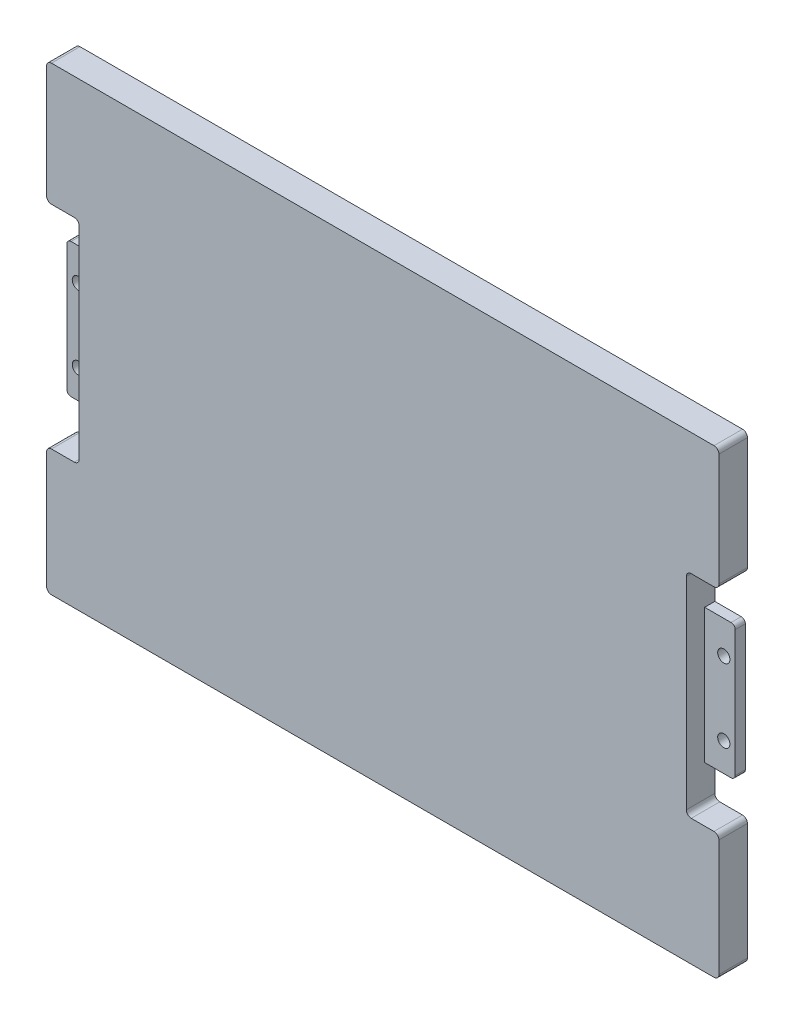
SolidWorks part; units mm, degrees
material "PBTP"
ref_plane "Front" through (0, 0, 0) normal (0, 0, 1) x (1, 0, 0)
ref_plane "Top" through (0, 0, 0) normal (0, 1, 0) x (1, 0, 0)
ref_plane "Right" through (0, 0, 0) normal (1, 0, 0) x (0, 0, -1)
sketch "Эскиз1" plane through (0, 0, 0) normal (0, 0, 1) x (1, 0, 0)
  line L0 (1.2018, 83) -> (6.7982, 83)
  line L1 (1.2018, 0) -> (163.7982, 0)
  line L2 (0, 1.2018) -> (0, 29.7982)
  line L3 (1.2018, 113) -> (163.7982, 113)
  line L4 (165, 1.2018) -> (165, 29.7982)
  line L5 (8, 81.7982) -> (8, 32.2018)
  line L6 (6.7982, 31) -> (1.2018, 31)
  line L7 (0, 84.2018) -> (0, 111.7982)
  line L8 (158.2018, 83) -> (163.7982, 83)
  line L9 (158.2018, 31) -> (163.7982, 31)
  line L10 (157, 81.7982) -> (157, 32.2018)
  line L11 (165, 84.2018) -> (165, 111.7982)
  arc A0 (0, 111.7982) -> (1.2018, 113) centre (1.2018, 111.7982) cw
  arc A1 (6.7982, 83) -> (8, 81.7982) centre (6.7982, 81.7982) cw
  arc A2 (1.2018, 83) -> (0, 84.2018) centre (1.2018, 84.2018) cw
  arc A3 (8, 32.2018) -> (6.7982, 31) centre (6.7982, 32.2018) cw
  arc A4 (1.2018, 31) -> (0, 29.7982) centre (1.2018, 29.7982) ccw
  arc A5 (1.2018, 0) -> (0, 1.2018) centre (1.2018, 1.2018) cw
  arc A6 (163.7982, 0) -> (165, 1.2018) centre (163.7982, 1.2018) ccw
  arc A7 (157, 32.2018) -> (158.2018, 31) centre (158.2018, 32.2018) ccw
  arc A8 (163.7982, 31) -> (165, 29.7982) centre (163.7982, 29.7982) cw
  arc A9 (158.2018, 83) -> (157, 81.7982) centre (158.2018, 81.7982) ccw
  arc A10 (163.7982, 83) -> (165, 84.2018) centre (163.7982, 84.2018) ccw
  arc A11 (163.7982, 113) -> (165, 111.7982) centre (163.7982, 111.7982) cw
  point P15 (0, 113)
  point P18 (8, 83)
  point P21 (0, 83)
  point P24 (8, 31)
  point P29 (0, 0)
  point P32 (165, 0)
  point P41 (165, 83)
  dimension "D9" = 1.2018
  dimension "D1" = 113
  dimension "D2" = 165
  dimension "D3" = 30
  dimension "D4" = 31
  dimension "D5" = 8
  dimension "D6" = 8
  dimension "D7" = 30
  dimension "D8" = 31
extrude "Бобышка-Вытянуть1" add sketch "Эскиз1" along normal blind 7
sketch "Эскиз2" plane through (0, 0, 0) normal (0, 0, -1) x (-1, 0, 0)
  line L0 (-163.7982, 113) -> (-1.2018, 113) construction
  line L1 (-161.7982, 111) -> (-3.2018, 111)
  line L2 (-163, 109.7982) -> (-163, 86.2018)
  line L3 (-161.7982, 2) -> (-3.2018, 2)
  line L4 (-2, 109.7982) -> (-2, 86.2018)
  line L5 (-1.2018, 0) -> (-163.7982, 0) construction
  line L6 (-165, 1.2018) -> (-165, 29.7982) construction
  line L7 (0, 111.7982) -> (0, 84.2018) construction
  line L8 (-161.7982, 85) -> (-156.2018, 85)
  line L9 (-155, 83.7982) -> (-155, 74.8)
  line L10 (-156.2018, 29) -> (-161.7982, 29)
  line L11 (-163, 27.7982) -> (-163, 3.2018)
  line L12 (-158.2018, 83) -> (-163.7982, 83) construction
  line L13 (-157, 32.2018) -> (-157, 81.7982) construction
  line L14 (-163.7982, 31) -> (-158.2018, 31) construction
  line L15 (-3.2018, 85) -> (-8.7982, 85)
  line L16 (-10, 83.7982) -> (-10, 30.2018)
  line L17 (-8.7982, 29) -> (-3.2018, 29)
  line L18 (-8, 81.7982) -> (-8, 32.2018) construction
  line L19 (-6.7982, 31) -> (-1.2018, 31) construction
  line L20 (-2, 27.7982) -> (-2, 3.2018)
  line L21 (-155, 74.8) -> (-155, 70.5)
  line L25 (-155, 70.5) -> (-155, 30.2018)
  circle A0 centre (-82.5, 57) radius 6
  arc A1 (-161.7982, 85) -> (-163, 86.2018) centre (-161.7982, 86.2018) cw
  arc A2 (-156.2018, 85) -> (-155, 83.7982) centre (-156.2018, 83.7982) cw
  arc A3 (-155, 30.2018) -> (-156.2018, 29) centre (-156.2018, 30.2018) cw
  arc A4 (-161.7982, 29) -> (-163, 27.7982) centre (-161.7982, 27.7982) ccw
  arc A5 (-163, 3.2018) -> (-161.7982, 2) centre (-161.7982, 3.2018) ccw
  arc A6 (-3.2018, 2) -> (-2, 3.2018) centre (-3.2018, 3.2018) ccw
  arc A7 (-3.2018, 29) -> (-2, 27.7982) centre (-3.2018, 27.7982) cw
  arc A8 (-10, 30.2018) -> (-8.7982, 29) centre (-8.7982, 30.2018) ccw
  arc A9 (-8.7982, 85) -> (-10, 83.7982) centre (-8.7982, 83.7982) ccw
  arc A10 (-3.2018, 85) -> (-2, 86.2018) centre (-3.2018, 86.2018) ccw
  arc A11 (-3.2018, 111) -> (-2, 109.7982) centre (-3.2018, 109.7982) cw
  arc A12 (-161.7982, 111) -> (-163, 109.7982) centre (-161.7982, 109.7982) ccw
  point P18 (-161, 83)
  point P31 (-4, 31)
  point P32 (-6, 29)
  point P45 (-155, 85)
  point P50 (-163, 29)
  point P57 (-2, 29)
  dimension "D12" = 12
  dimension "D17" = 1.2018
  dimension "D1" = 2
  dimension "D2" = 2
  dimension "D3" = 2
  dimension "D4" = 2
  dimension "D5" = 2
  dimension "D6" = 2
  dimension "D7" = 2
  dimension "D8" = 2
  dimension "D9" = 2
  dimension "D10" = 2
  dimension "D11" = 56
  dimension "D13" = 82.5
extrude "Вырез-Вытянуть1" cut sketch "Эскиз2" against normal blind 5.8
sketch "Эскиз3" plane through (0, 0, 5.8) normal (0, 0, -1) x (-1, 0, 0)
  line L0 (-1.2018, 0) -> (-163.7982, 0) construction
  line L1 (-120, 31) -> (-103, 31)
  line L2 (-121, 30) -> (-121, 19)
  line L3 (-120, 18) -> (-103, 18)
  line L4 (-102, 30) -> (-102, 19)
  line L5 (-165, 1.2018) -> (-165, 29.7982) construction
  line L6 (-41.4032, 94.6438) -> (-44.49, 94.6438)
  line L7 (-52.1501, 97.2393) -> (-39.1501, 97.2393)
  line L8 (-53.1501, 96.2393) -> (-53.1501, 83.2393)
  line L9 (-52.1501, 82.2393) -> (-39.1501, 82.2393)
  line L10 (-38.1501, 96.2393) -> (-38.1501, 83.2393)
  line L11 (-44.49, 94.6438) -> (-48.7847, 93.6372)
  line L12 (-48.7847, 93.6372) -> (-48.7847, 92.6306)
  line L13 (-48.7847, 92.6306) -> (-44.49, 93.6372)
  line L14 (-44.49, 93.6372) -> (-41.4032, 93.6372)
  line L15 (-41.4032, 93.6372) -> (-41.4032, 94.6438)
  line L16 (-48.7847, 91.7748) -> (-44.49, 92.6306)
  line L17 (-44.49, 92.6306) -> (-44.49, 91.7748)
  line L18 (-44.49, 91.7748) -> (-48.7847, 90.919)
  line L19 (-48.7847, 90.919) -> (-48.7847, 91.7748)
  line L20 (-48.7847, 90.0551) -> (-44.49, 90.9109)
  line L21 (-44.49, 90.9109) -> (-44.49, 90.0551)
  line L22 (-44.49, 90.0551) -> (-48.7847, 89.0679)
  line L23 (-48.7847, 90.0551) -> (-48.7847, 89.0679)
  line L24 (-48.7847, 88.2165) -> (-44.49, 89.0679)
  line L25 (-44.49, 89.0679) -> (-41.4032, 89.0679)
  line L26 (-41.4032, 89.0679) -> (-41.4032, 88.3169)
  line L27 (-41.4032, 88.3169) -> (-44.3412, 88.3169)
  line L28 (-44.3412, 88.3169) -> (-48.7847, 87.436)
  line L29 (-48.7847, 87.436) -> (-48.7847, 88.2165)
  line L30 (-48.6096, 93.8881) -> (-44.8588, 94.806)
  line L31 (-44.8588, 94.806) -> (-44.8588, 95.9138)
  line L32 (-44.8588, 95.9138) -> (-46.7342, 95.17)
  line L33 (-46.7342, 95.17) -> (-48.6096, 95.7398)
  line L34 (-48.6096, 95.7398) -> (-48.6096, 93.8881)
  line L35 (-48.6096, 87.0068) -> (-44.8588, 87.7157)
  line L36 (-44.8588, 87.7157) -> (-44.8588, 86.3281)
  line L37 (-44.8588, 86.3281) -> (-46.7342, 86.675)
  line L38 (-46.7342, 86.675) -> (-48.6096, 85.77)
  line L39 (-48.6096, 85.77) -> (-48.6096, 87.0068)
  arc A0 (-103, 18) -> (-102, 19) centre (-103, 19) ccw
  arc A1 (-121, 19) -> (-120, 18) centre (-120, 19) ccw
  arc A2 (-103, 31) -> (-102, 30) centre (-103, 30) cw
  arc A3 (-120, 31) -> (-121, 30) centre (-120, 30) ccw
  arc A4 (-39.1501, 97.2393) -> (-38.1501, 96.2393) centre (-39.1501, 96.2393) cw
  arc A5 (-39.1501, 82.2393) -> (-38.1501, 83.2393) centre (-39.1501, 83.2393) ccw
  arc A6 (-53.1501, 83.2393) -> (-52.1501, 82.2393) centre (-52.1501, 83.2393) ccw
  arc A7 (-52.1501, 97.2393) -> (-53.1501, 96.2393) centre (-52.1501, 96.2393) ccw
  point P10 (-102, 18)
  point P13 (-121, 18)
  point P16 (-102, 31)
  point P25 (-38.1501, 97.2393)
  point P30 (-53.1501, 82.2393)
  point P33 (-53.1501, 97.2393)
  dimension "D7" = 1
  dimension "D10" = 1
  dimension "D1" = 13
  dimension "D2" = 19
  dimension "D3" = 18
  dimension "D4" = 31
  dimension "D5" = 44
  dimension "D6" = 63
  dimension "D8" = 15
  dimension "D9" = 15
extrude "Вырез-Вытянуть2" cut sketch "Эскиз3" against normal blind 0.2
sketch "Эскиз4" plane through (0, 0, 0) normal (0, 0, -1) x (-1, 0, 0)
  line L0 (-163.5, 73) -> (-157, 73)
  line L1 (-157, 32.2018) -> (-157, 81.7982) construction
  line L2 (-164.5, 72) -> (-164.5, 41)
  line L3 (-163.5, 40) -> (-157, 40)
  line L4 (-163.7982, 113) -> (-1.2018, 113) construction
  line L5 (-1.2018, 0) -> (-163.7982, 0) construction
  line L6 (-8, 73) -> (-1.5, 73)
  line L7 (-8, 81.7982) -> (-8, 32.2018) construction
  line L8 (-0.5, 72) -> (-0.5, 41)
  line L9 (-1.5, 40) -> (-8, 40)
  line L10 (-8, 73) -> (-8, 40)
  line L18 (0, 1.2018) -> (0, 29.7982)
  line L19 (-1.2018, 31) -> (-6.7982, 31)
  line L20 (-8, 32.2018) -> (-8, 81.7982)
  line L21 (-6.7982, 83) -> (-1.2018, 83)
  line L22 (0, 84.2018) -> (0, 111.7982)
  line L23 (-1.2018, 113) -> (-163.7982, 113)
  line L24 (-165, 111.7982) -> (-165, 84.2018)
  line L25 (-163.7982, 83) -> (-158.2018, 83)
  line L26 (-157, 81.7982) -> (-157, 32.2018)
  line L27 (-158.2018, 31) -> (-163.7982, 31)
  line L28 (-165, 29.7982) -> (-165, 1.2018)
  line L29 (-163.7982, 0) -> (-1.2018, 0)
  line L38 (-157, 73) -> (-157, 40)
  circle A0 centre (-161.7, 65) radius 1.5
  circle A1 centre (-161.7, 47) radius 1.5
  circle A2 centre (-3.3, 65) radius 1.5
  circle A3 centre (-3.3, 47) radius 1.5
  arc A4 (-0.5, 41) -> (-1.5, 40) centre (-1.5, 41) cw
  arc A5 (-164.5, 41) -> (-163.5, 40) centre (-163.5, 41) ccw
  arc A6 (-163.5, 73) -> (-164.5, 72) centre (-163.5, 72) ccw
  arc A7 (-1.5, 73) -> (-0.5, 72) centre (-1.5, 72) cw
  arc A16 (0, 111.7982) -> (-1.2018, 113) centre (-1.2018, 111.7982) ccw
  arc A17 (0, 111.7982) -> (-1.2018, 113) centre (-1.2018, 111.7982) ccw
  arc A18 (-163.7982, 113) -> (-165, 111.7982) centre (-163.7982, 111.7982) ccw
  arc A19 (-163.7982, 113) -> (-165, 111.7982) centre (-163.7982, 111.7982) ccw
  arc A20 (-165, 84.2018) -> (-163.7982, 83) centre (-163.7982, 84.2018) ccw
  arc A21 (-165, 84.2018) -> (-163.7982, 83) centre (-163.7982, 84.2018) ccw
  arc A22 (-157, 81.7982) -> (-158.2018, 83) centre (-158.2018, 81.7982) ccw
  arc A23 (-157, 81.7982) -> (-158.2018, 83) centre (-158.2018, 81.7982) ccw
  arc A24 (-158.2018, 31) -> (-157, 32.2018) centre (-158.2018, 32.2018) ccw
  arc A25 (-158.2018, 31) -> (-157, 32.2018) centre (-158.2018, 32.2018) ccw
  arc A26 (-163.7982, 31) -> (-165, 29.7982) centre (-163.7982, 29.7982) ccw
  arc A27 (-163.7982, 31) -> (-165, 29.7982) centre (-163.7982, 29.7982) ccw
  arc A28 (-165, 1.2018) -> (-163.7982, 0) centre (-163.7982, 1.2018) ccw
  arc A29 (-165, 1.2018) -> (-163.7982, 0) centre (-163.7982, 1.2018) ccw
  arc A30 (-1.2018, 0) -> (0, 1.2018) centre (-1.2018, 1.2018) ccw
  arc A31 (-1.2018, 0) -> (0, 1.2018) centre (-1.2018, 1.2018) ccw
  arc A32 (0, 29.7982) -> (-1.2018, 31) centre (-1.2018, 29.7982) ccw
  arc A33 (0, 29.7982) -> (-1.2018, 31) centre (-1.2018, 29.7982) ccw
  arc A34 (-8, 32.2018) -> (-6.7982, 31) centre (-6.7982, 32.2018) ccw
  arc A35 (-8, 32.2018) -> (-6.7982, 31) centre (-6.7982, 32.2018) ccw
  arc A36 (-6.7982, 83) -> (-8, 81.7982) centre (-6.7982, 81.7982) ccw
  arc A37 (-6.7982, 83) -> (-8, 81.7982) centre (-6.7982, 81.7982) ccw
  arc A38 (-1.2018, 83) -> (0, 84.2018) centre (-1.2018, 84.2018) ccw
  arc A39 (-1.2018, 83) -> (0, 84.2018) centre (-1.2018, 84.2018) ccw
  dimension "D8" = 48
  dimension "D9" = 18
  dimension "D15" = 3
  dimension "D16" = 3
  dimension "D17" = 3
  dimension "D18" = 3
  dimension "D21" = 1
  dimension "D22" = 1
  dimension "D1" = 7.5
  dimension "D2" = 40
  dimension "D3" = 40
  dimension "D5" = 7.5
  dimension "D6" = 40
  dimension "D7" = 40
  dimension "D10" = 2.8
  dimension "D11" = 2.8
  dimension "D12" = 2.8
  dimension "D13" = 48
  dimension "D14" = 66
  dimension "D19" = 158.4
  dimension "D20" = 2.8
  dimension "D4" = 0
fillet "Скругление1" radius 1 24 edges at (155, 57, 5.8) (155.352, 29.352, 5.8) (159, 29, 5.8) (162.648, 28.648, 5.8) (163, 15.5, 5.8) (162.648, 2.352, 5.8) (82.5, 2, 5.8) (2.352, 2.352, 5.8) (2, 15.5, 5.8) (2.352, 28.648, 5.8) (6, 29, 5.8) (9.648, 29.352, 5.8) (10, 57, 5.8) (9.648, 84.648, 5.8) (6, 85, 5.8) (2.352, 85.352, 5.8) (2, 98, 5.8) (2.352, 110.648, 5.8) (155.352, 84.648, 5.8) (159, 85, 5.8) (162.648, 85.352, 5.8) (163, 98, 5.8) (162.648, 110.648, 5.8) (82.5, 111, 5.8)
extrude "Бобышка-Вытянуть3" add sketch "Эскиз4" against normal blind 2.5 contours L6 L10 L9 L8 A3 A2 | L38 L0 L2 L3 A1 A0 region at (160.6858, 56.5303, 0) region at (4.3142, 56.5303, 0)
sketch "Эскиз5" plane through (0, 0, 0) normal (0, 0, -1) x (-1, 0, 0)
  line L0 (-155, 30.2018) -> (-155, 83.7982) construction
  line L1 (-155, 70.5) -> (-156.5, 70.5)
  line L2 (-155, 70.5) -> (-155, 74.8)
  line L3 (-155, 74.8) -> (-156.5, 74.8)
  line L4 (-156.5, 70.5) -> (-156.5, 74.8)
  line L5 (-165, 84.2018) -> (-165, 111.7982) construction
  line L6 (-163.7982, 113) -> (-1.2018, 113) construction
  point P8 (-156.5, 72.65)
  dimension "D1" = 8.5
  dimension "D2" = 42.5
  dimension "D3" = 38.2
extrude "Вырез-Вытянуть3" cut sketch "Эскиз5" against normal blind 2.5
sketch "Эскиз6" plane through (0, 0, 0) normal (0, 0, -1) x (-1, 0, 0)
  line L0 (-155, 83.7982) -> (-155, 74.8) construction
  line L1 (-155, 83) -> (-158.1743, 83)
  line L2 (-155, 83) -> (-155, 80)
  line L3 (-155, 80) -> (-158.1743, 80)
  line L4 (-158.1743, 83) -> (-158.1743, 80)
  line L5 (-163.7982, 113) -> (-1.2018, 113) construction
  point P8 (-156.5871, 83)
  dimension "D1" = 30
  dimension "D2" = 33
extrude "Вырез-Вытянуть4" cut sketch "Эскиз6" against normal blind 1
